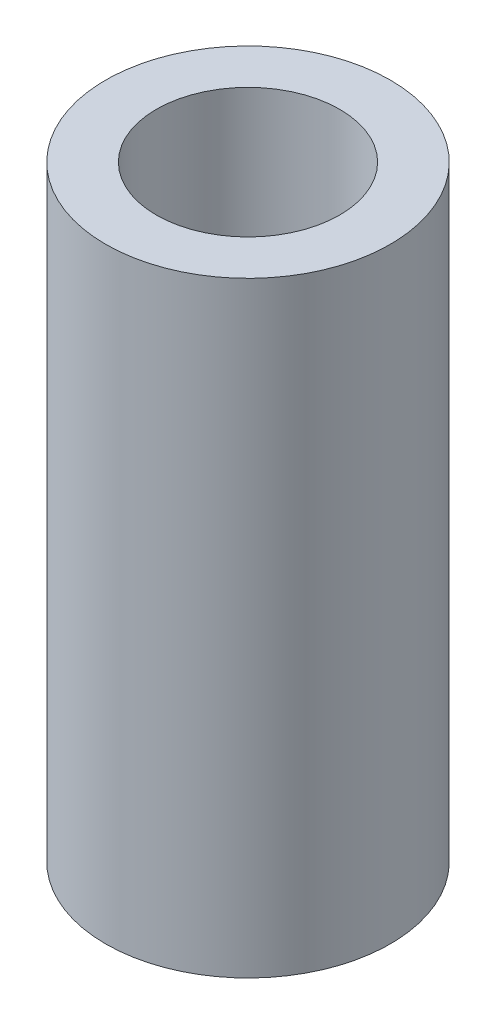
SolidWorks part; units mm, degrees
ref_plane "Front Plane" through (0, 0, 0) normal (0, 0, 1) x (1, 0, 0)
ref_plane "Top Plane" through (0, 0, 0) normal (0, 1, 0) x (1, 0, 0)
ref_plane "Right Plane" through (0, 0, 0) normal (1, 0, 0) x (0, 0, -1)
sketch "Sketch1" plane through (0, 0, 0) normal (0, 1, 0) x (1, 0, 0)
  circle A0 centre (0, 0) radius 15
  dimension "SLEEVE_OD" = 30
extrude "Boss-Extrude1" add sketch "Sketch1" along normal blind 63.8672
sketch "Sketch2" plane through (0, 0, 0) normal (0, 1, 0) x (1, 0, 0)
  circle A0 centre (0, 0) radius 9.6618
  dimension "BORE_D" = 19.3236
extrude "Cut-Extrude1" cut sketch "Sketch2" along normal through all
chamfer "Chamfer1" distance 2.7669 angle 60 rebuild error yes
